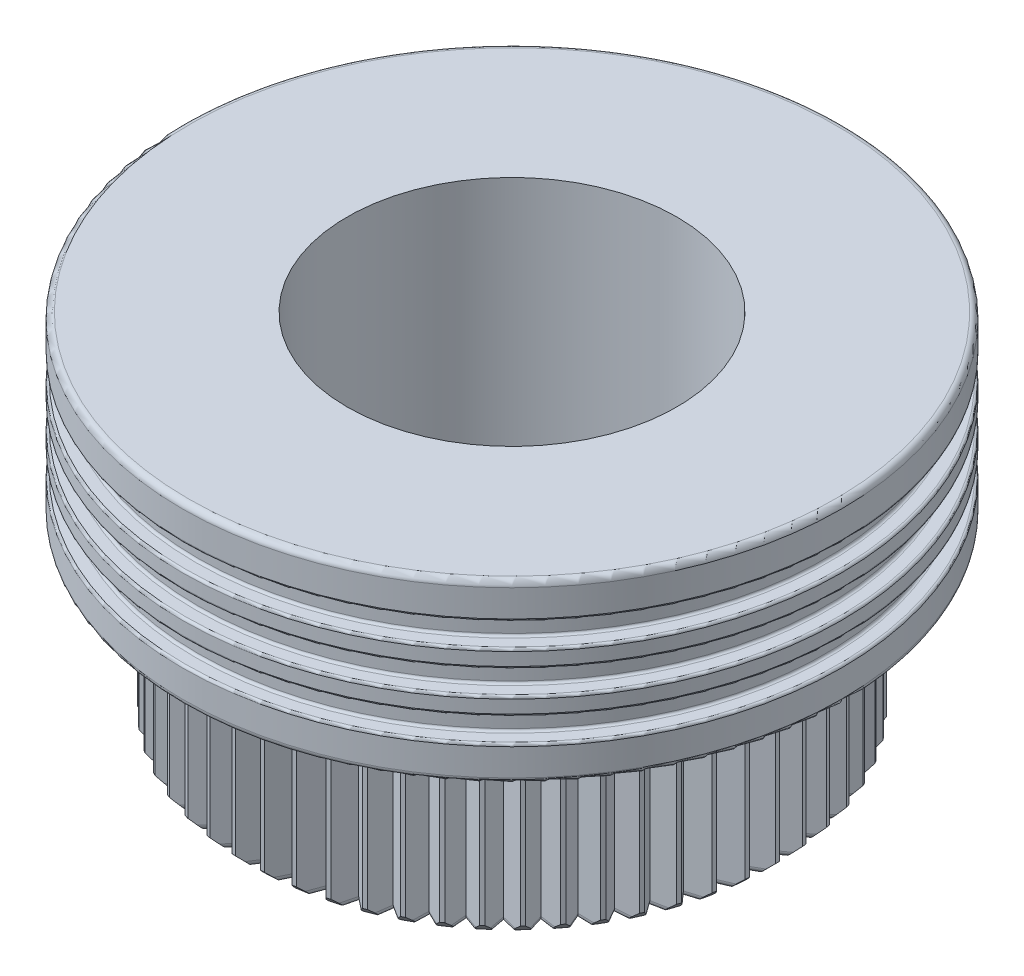
SolidWorks part; units mm, degrees
ref_plane "前视基准面" through (0, 0, 0) normal (0, 0, 1) x (1, 0, 0)
ref_plane "上视基准面" through (0, 0, 0) normal (0, 1, 0) x (1, 0, 0)
ref_plane "右视基准面" through (0, 0, 0) normal (1, 0, 0) x (0, 0, -1)
sketch "草图1" plane through (0, 0, 0) normal (0, 1, 0) x (1, 0, 0)
  circle A0 centre (0, 0) radius 2.25
  circle A1 centre (0, 0) radius 1.2
  dimension "D1" = 2.4
  dimension "D2" = 4.5
extrude "凸台-拉伸1" add sketch "草图1" along normal blind 1.53
sketch "草图2" plane through (0, 1.53, 0) normal (0, 1, 0) x (1, 0, 0)
  circle A0 centre (0, 0) radius 1.2 construction
  circle A1 centre (0, 0) radius 1.2
  circle A2 centre (0, 0) radius 2.8
  dimension "D1" = 5.6
extrude "凸台-拉伸2" add sketch "草图2" along normal blind 1.5
hole_wizard "M3 螺纹孔1" positions "草图3" profile "草图4" tap size "M3" standard "GB" end condition through all
sketch "草图3" plane through (0, 3.03, 0) normal (0, 1, 0) x (1, 0, 0)
  point P0 (0, 0)
sketch "草图4" plane through (0, 3.03, 0) normal (1, 0, 0) x (0, 0, 1)
  line L0 (0, 0) -> (0, 3.03)
  line L1 (0, 3.03) -> (1.4, 3.03)
  line L2 (1.4, 3.03) -> (1.4, 0)
  line L5 (1.4, 0) -> (0, 0)
  line L11 (0, -6.35) -> (0, 107.95) construction
  dimension "通孔螺纹孔钻头直径" = 2.8
  dimension "通孔螺纹孔钻头深度" = 3.03
cosmetic thread "孔螺蚊线1" parameters "D2"=3
chamfer "倒角1" distance 0.1 angle 45 1 edges at (0, 0, 2.25)
sketch "草图5" plane through (0, 0, 0) normal (0, -1, 0) x (1, 0, 0)
  line L0 (-0.1033, 2.2519) -> (0.0051, 2.0833)
  line L1 (0.0051, 2.0833) -> (0.1135, 2.2519)
  line L2 (0.1135, 2.2519) -> (-0.1033, 2.2519)
  line L3 (0.3563, 2.2264) -> (0.1408, 2.2499)
  line L4 (0.1408, 2.2499) -> (0.2303, 2.0706)
  line L5 (0.2303, 2.0706) -> (0.3563, 2.2264)
  line L6 (0.5949, 2.1749) -> (0.3832, 2.2215)
  line L7 (0.3832, 2.2215) -> (0.4528, 2.0335)
  line L8 (0.4528, 2.0335) -> (0.5949, 2.1749)
  line L9 (0.8266, 2.0978) -> (0.6212, 2.167)
  line L10 (0.6212, 2.167) -> (0.67, 1.9726)
  line L11 (0.67, 1.9726) -> (0.8266, 2.0978)
  line L12 (1.0485, 1.9961) -> (0.8518, 2.0871)
  line L13 (0.8518, 2.0871) -> (0.8794, 1.8886)
  line L14 (0.8794, 1.8886) -> (1.0485, 1.9961)
  line L15 (1.2582, 1.8711) -> (1.0725, 1.9828)
  line L16 (1.0725, 1.9828) -> (1.0784, 1.7825)
  line L17 (1.0784, 1.7825) -> (1.2582, 1.8711)
  line L18 (1.4531, 1.7241) -> (1.2806, 1.8552)
  line L19 (1.2806, 1.8552) -> (1.2648, 1.6554)
  line L20 (1.2648, 1.6554) -> (1.4531, 1.7241)
  line L21 (1.631, 1.5568) -> (1.4737, 1.7059)
  line L22 (1.4737, 1.7059) -> (1.4364, 1.509)
  line L23 (1.4364, 1.509) -> (1.631, 1.5568)
  line L24 (1.7898, 1.3714) -> (1.6495, 1.5366)
  line L25 (1.6495, 1.5366) -> (1.5911, 1.3448)
  line L26 (1.5911, 1.3448) -> (1.7898, 1.3714)
  line L27 (1.9276, 1.1698) -> (1.8059, 1.3492)
  line L28 (1.8059, 1.3492) -> (1.7272, 1.1649)
  line L29 (1.7272, 1.1649) -> (1.9276, 1.1698)
  line L30 (2.0427, 0.9546) -> (1.9412, 1.1461)
  line L31 (1.9412, 1.1461) -> (1.843, 0.9713)
  line L32 (1.843, 0.9713) -> (2.0427, 0.9546)
  line L33 (2.134, 0.7281) -> (2.0537, 0.9295)
  line L34 (2.0537, 0.9295) -> (1.9373, 0.7664)
  line L35 (1.9373, 0.7664) -> (2.134, 0.7281)
  line L36 (2.2002, 0.4931) -> (2.1422, 0.702)
  line L37 (2.1422, 0.702) -> (2.0088, 0.5524)
  line L38 (2.0088, 0.5524) -> (2.2002, 0.4931)
  line L39 (2.2406, 0.2523) -> (2.2055, 0.4662)
  line L40 (2.2055, 0.4662) -> (2.0567, 0.332)
  line L41 (2.0567, 0.332) -> (2.2406, 0.2523)
  line L42 (2.2548, 0.0086) -> (2.243, 0.225)
  line L43 (2.243, 0.225) -> (2.0806, 0.1077)
  line L44 (2.0806, 0.1077) -> (2.2548, 0.0086)
  line L45 (2.2425, -0.2352) -> (2.2542, -0.0188)
  line L46 (2.2542, -0.0188) -> (2.08, -0.1179)
  line L47 (2.08, -0.1179) -> (2.2425, -0.2352)
  line L48 (2.2039, -0.4763) -> (2.239, -0.2624)
  line L49 (2.239, -0.2624) -> (2.0551, -0.3421)
  line L50 (2.0551, -0.3421) -> (2.2039, -0.4763)
  line L51 (2.1395, -0.7118) -> (2.1975, -0.5029)
  line L52 (2.1975, -0.5029) -> (2.006, -0.5623)
  line L53 (2.006, -0.5623) -> (2.1395, -0.7118)
  line L54 (2.05, -0.9389) -> (2.1302, -0.7376)
  line L55 (2.1302, -0.7376) -> (1.9335, -0.7759)
  line L56 (1.9335, -0.7759) -> (2.05, -0.9389)
  line L57 (1.9364, -1.1551) -> (2.038, -0.9636)
  line L58 (2.038, -0.9636) -> (1.8383, -0.9804)
  line L59 (1.8383, -0.9804) -> (1.9364, -1.1551)
  line L60 (1.8002, -1.3577) -> (1.9218, -1.1783)
  line L61 (1.9218, -1.1783) -> (1.7215, -1.1734)
  line L62 (1.7215, -1.1734) -> (1.8002, -1.3577)
  line L63 (1.6429, -1.5443) -> (1.7832, -1.3791)
  line L64 (1.7832, -1.3791) -> (1.5845, -1.3526)
  line L65 (1.5845, -1.3526) -> (1.6429, -1.5443)
  line L66 (1.4663, -1.7129) -> (1.6236, -1.5639)
  line L67 (1.6236, -1.5639) -> (1.429, -1.516)
  line L68 (1.429, -1.516) -> (1.4663, -1.7129)
  line L69 (1.2725, -1.8614) -> (1.445, -1.7302)
  line L70 (1.445, -1.7302) -> (1.2567, -1.6616)
  line L71 (1.2567, -1.6616) -> (1.2725, -1.8614)
  line L72 (1.0638, -1.9881) -> (1.2495, -1.8763)
  line L73 (1.2495, -1.8763) -> (1.0697, -1.7877)
  line L74 (1.0697, -1.7877) -> (1.0638, -1.9881)
  line L75 (0.8426, -2.0914) -> (1.0393, -2.0004)
  line L76 (1.0393, -2.0004) -> (0.8701, -1.8929)
  line L77 (0.8701, -1.8929) -> (0.8426, -2.0914)
  line L78 (0.6115, -2.1703) -> (0.8169, -2.1011)
  line L79 (0.8169, -2.1011) -> (0.6604, -1.9759)
  line L80 (0.6604, -1.9759) -> (0.6115, -2.1703)
  line L81 (0.3733, -2.2237) -> (0.585, -2.1771)
  line L82 (0.585, -2.1771) -> (0.4429, -2.0357)
  line L83 (0.4429, -2.0357) -> (0.3733, -2.2237)
  line L84 (0.1307, -2.251) -> (0.3461, -2.2275)
  line L85 (0.3461, -2.2275) -> (0.2202, -2.0717)
  line L86 (0.2202, -2.0717) -> (0.1307, -2.251)
  line L87 (-0.1135, -2.2519) -> (0.1033, -2.2519)
  line L88 (0.1033, -2.2519) -> (-0.0051, -2.0833)
  line L89 (-0.0051, -2.0833) -> (-0.1135, -2.2519)
  line L90 (-0.3563, -2.2264) -> (-0.1408, -2.2499)
  line L91 (-0.1408, -2.2499) -> (-0.2303, -2.0706)
  line L92 (-0.2303, -2.0706) -> (-0.3563, -2.2264)
  line L93 (-0.5949, -2.1749) -> (-0.3832, -2.2215)
  line L94 (-0.3832, -2.2215) -> (-0.4528, -2.0335)
  line L95 (-0.4528, -2.0335) -> (-0.5949, -2.1749)
  line L96 (-0.8266, -2.0978) -> (-0.6212, -2.167)
  line L97 (-0.6212, -2.167) -> (-0.67, -1.9726)
  line L98 (-0.67, -1.9726) -> (-0.8266, -2.0978)
  line L99 (-1.0485, -1.9961) -> (-0.8518, -2.0871)
  line L100 (-0.8518, -2.0871) -> (-0.8794, -1.8886)
  line L101 (-0.8794, -1.8886) -> (-1.0485, -1.9961)
  line L102 (-1.2582, -1.8711) -> (-1.0725, -1.9828)
  line L103 (-1.0725, -1.9828) -> (-1.0784, -1.7825)
  line L104 (-1.0784, -1.7825) -> (-1.2582, -1.8711)
  line L105 (-1.4531, -1.7241) -> (-1.2806, -1.8552)
  line L106 (-1.2806, -1.8552) -> (-1.2648, -1.6554)
  line L107 (-1.2648, -1.6554) -> (-1.4531, -1.7241)
  line L108 (-1.631, -1.5568) -> (-1.4737, -1.7059)
  line L109 (-1.4737, -1.7059) -> (-1.4364, -1.509)
  line L110 (-1.4364, -1.509) -> (-1.631, -1.5568)
  line L111 (-1.7898, -1.3714) -> (-1.6495, -1.5366)
  line L112 (-1.6495, -1.5366) -> (-1.5911, -1.3448)
  line L113 (-1.5911, -1.3448) -> (-1.7898, -1.3714)
  line L114 (-1.9276, -1.1698) -> (-1.8059, -1.3492)
  line L115 (-1.8059, -1.3492) -> (-1.7272, -1.1649)
  line L116 (-1.7272, -1.1649) -> (-1.9276, -1.1698)
  line L117 (-2.0427, -0.9546) -> (-1.9412, -1.1461)
  line L118 (-1.9412, -1.1461) -> (-1.843, -0.9713)
  line L119 (-1.843, -0.9713) -> (-2.0427, -0.9546)
  line L120 (-2.134, -0.7281) -> (-2.0537, -0.9295)
  line L121 (-2.0537, -0.9295) -> (-1.9373, -0.7664)
  line L122 (-1.9373, -0.7664) -> (-2.134, -0.7281)
  line L123 (-2.2002, -0.4931) -> (-2.1422, -0.702)
  line L124 (-2.1422, -0.702) -> (-2.0088, -0.5524)
  line L125 (-2.0088, -0.5524) -> (-2.2002, -0.4931)
  line L126 (-2.2406, -0.2523) -> (-2.2055, -0.4662)
  line L127 (-2.2055, -0.4662) -> (-2.0567, -0.332)
  line L128 (-2.0567, -0.332) -> (-2.2406, -0.2523)
  line L129 (-2.2548, -0.0086) -> (-2.243, -0.225)
  line L130 (-2.243, -0.225) -> (-2.0806, -0.1077)
  line L131 (-2.0806, -0.1077) -> (-2.2548, -0.0086)
  line L132 (-2.2425, 0.2352) -> (-2.2542, 0.0188)
  line L133 (-2.2542, 0.0188) -> (-2.08, 0.1179)
  line L134 (-2.08, 0.1179) -> (-2.2425, 0.2352)
  line L135 (-2.2039, 0.4763) -> (-2.239, 0.2624)
  line L136 (-2.239, 0.2624) -> (-2.0551, 0.3421)
  line L137 (-2.0551, 0.3421) -> (-2.2039, 0.4763)
  line L138 (-2.1395, 0.7118) -> (-2.1975, 0.5029)
  line L139 (-2.1975, 0.5029) -> (-2.006, 0.5623)
  line L140 (-2.006, 0.5623) -> (-2.1395, 0.7118)
  line L141 (-2.05, 0.9389) -> (-2.1302, 0.7376)
  line L142 (-2.1302, 0.7376) -> (-1.9335, 0.7759)
  line L143 (-1.9335, 0.7759) -> (-2.05, 0.9389)
  line L144 (-1.9364, 1.1551) -> (-2.038, 0.9636)
  line L145 (-2.038, 0.9636) -> (-1.8383, 0.9804)
  line L146 (-1.8383, 0.9804) -> (-1.9364, 1.1551)
  line L147 (-1.8002, 1.3577) -> (-1.9218, 1.1783)
  line L148 (-1.9218, 1.1783) -> (-1.7215, 1.1734)
  line L149 (-1.7215, 1.1734) -> (-1.8002, 1.3577)
  line L150 (-1.6429, 1.5443) -> (-1.7832, 1.3791)
  line L151 (-1.7832, 1.3791) -> (-1.5845, 1.3526)
  line L152 (-1.5845, 1.3526) -> (-1.6429, 1.5443)
  line L153 (-1.4663, 1.7129) -> (-1.6236, 1.5639)
  line L154 (-1.6236, 1.5639) -> (-1.429, 1.516)
  line L155 (-1.429, 1.516) -> (-1.4663, 1.7129)
  line L156 (-1.2725, 1.8614) -> (-1.445, 1.7302)
  line L157 (-1.445, 1.7302) -> (-1.2567, 1.6616)
  line L158 (-1.2567, 1.6616) -> (-1.2725, 1.8614)
  line L159 (-1.0638, 1.9881) -> (-1.2495, 1.8763)
  line L160 (-1.2495, 1.8763) -> (-1.0697, 1.7877)
  line L161 (-1.0697, 1.7877) -> (-1.0638, 1.9881)
  line L162 (-0.8426, 2.0914) -> (-1.0393, 2.0004)
  line L163 (-1.0393, 2.0004) -> (-0.8701, 1.8929)
  line L164 (-0.8701, 1.8929) -> (-0.8426, 2.0914)
  line L165 (-0.6115, 2.1703) -> (-0.8169, 2.1011)
  line L166 (-0.8169, 2.1011) -> (-0.6604, 1.9759)
  line L167 (-0.6604, 1.9759) -> (-0.6115, 2.1703)
  line L168 (-0.3733, 2.2237) -> (-0.585, 2.1771)
  line L169 (-0.585, 2.1771) -> (-0.4429, 2.0357)
  line L170 (-0.4429, 2.0357) -> (-0.3733, 2.2237)
  line L171 (-0.1307, 2.251) -> (-0.3461, 2.2275)
  line L172 (-0.3461, 2.2275) -> (-0.2202, 2.0717)
  line L173 (-0.2202, 2.0717) -> (-0.1307, 2.251)
  point P176 (0, 0)
  dimension "D1" = 58
extrude "切除-拉伸1" cut sketch "草图5" against normal up to surface (1.53 mm away) up to face at (0, 1.53, 2.25)
fillet "圆角1" radius 0.05 177 edges at (0, 1.53, 2.8) (0, 3.03, 2.8) (0, 0, 1.4) (2.0437, 0, -0.5506) (2.0322, 0, -0.5916) (2.0358, 0, -0.6913) (1.9722, 0, -0.7683) (1.9563, 0, -0.8078) (1.9492, 0, -0.9073) (1.8776, 0, -0.9771) (1.8575, 0, -1.0146) (1.8396, 0, -1.1128) (1.7609, 0, -1.1743) (1.7369, 0, -1.2095) (1.7085, 0, -1.3051) (1.6236, 0, -1.3578) (1.596, 0, -1.3902) (1.5574, 0, -1.4822) (1.4673, 0, -1.5254) (1.4363, 0, -1.5546) (1.388, 0, -1.6419) (1.2938, 0, -1.6751) (1.2598, 0, -1.7008) (1.2024, 0, -1.7824) (1.1051, 0, -1.8052) (1.0685, 0, -1.827) (1.0026, 0, -1.9019) (0.9034, 0, -1.9141) (0.8647, 0, -1.9319) (0.7911, 0, -1.9992) (0.6912, 0, -2.0005) (0.6508, 0, -2.014) (0.5703, 0, -2.073) (0.4708, 0, -2.0635) (0.4292, 0, -2.0726) (0.3429, 0, -2.1225) (0.245, 0, -2.1023) (0.2026, 0, -2.1068) (0.1114, 0, -2.1471) (0.0162, 0, -2.1165) (-0.0264, 0, -2.1164) (-0.1214, 0, -2.1466) (-0.2127, 0, -2.1058) (-0.255, 0, -2.1011) (-0.3528, 0, -2.1209) (-0.4391, 0, -2.0705) (-0.4807, 0, -2.0613) (-0.58, 0, -2.0703) (-0.6604, 0, -2.0109) (-0.7007, 0, -1.9972) (-0.8005, 0, -1.9954) (-0.874, 0, -1.9277) (-0.9126, 0, -1.9097) (-1.0115, 0, -1.8972) (-1.0773, 0, -1.8219) (-1.1137, 0, -1.7999) (-1.2107, 0, -1.7767) (-1.2679, 0, -1.6948) (-1.3018, 0, -1.6689) (-1.3957, 0, -1.6354) (-1.4437, 0, -1.5477) (-1.4746, 0, -1.5184) (-1.5643, 0, -1.4749) (-1.6026, 0, -1.3826) (-1.6301, 0, -1.35) (-1.7146, 0, -1.2971) (-1.7427, 0, -1.2012) (-1.7665, 0, -1.1659) (-1.8448, 0, -1.1041) (-1.8624, 0, -1.0057) (-1.8822, 0, -0.9681) (-1.9534, 0, -0.8982) (-1.9602, 0, -0.7985) (-1.9758, 0, -0.7589) (-2.0391, 0, -0.6817) (-2.035, 0, -0.5819) (-2.0463, 0, -0.5408) (-2.1008, 0, -0.4573) (-2.086, 0, -0.3584) (-2.0928, 0, -0.3164) (-2.1379, 0, -0.2274) (-2.1125, 0, -0.1308) (-2.1147, 0, -0.0883) (-2.15, 0, 0.005) (-2.1143, 0, 0.0984) (-2.1119, 0, 0.1409) (-2.1368, 0, 0.2375) (-2.0912, 0, 0.3264) (-2.0843, 0, 0.3684) (-2.0986, 0, 0.4671) (-2.0437, 0, 0.5506) (-2.0322, 0, 0.5916) (-2.0358, 0, 0.6913) (-1.9722, 0, 0.7683) (-1.9563, 0, 0.8078) (-1.9492, 0, 0.9073) (-1.8776, 0, 0.9771) (-1.8575, 0, 1.0146) (-1.8396, 0, 1.1128) (-1.7609, 0, 1.1743) (-1.7369, 0, 1.2095) (-1.7085, 0, 1.3051) (-1.6236, 0, 1.3578) (-1.596, 0, 1.3902) (-1.5574, 0, 1.4822) (-1.4673, 0, 1.5254) (-1.4363, 0, 1.5546) (-1.388, 0, 1.6419) (-1.2938, 0, 1.6751) (-1.2598, 0, 1.7008) (-1.2024, 0, 1.7824) (-1.1051, 0, 1.8052) (-1.0685, 0, 1.827) (-1.0026, 0, 1.9019) (-0.9034, 0, 1.9141) (-0.8647, 0, 1.9319) (-0.7911, 0, 1.9992) (-0.6912, 0, 2.0005) (-0.6508, 0, 2.014) (-0.5703, 0, 2.073) (-0.4708, 0, 2.0635) (-0.4292, 0, 2.0726) (-0.3429, 0, 2.1225) (-0.245, 0, 2.1023) (-0.2026, 0, 2.1068) (-0.1114, 0, 2.1471) (-0.0162, 0, 2.1165) (0.0264, 0, 2.1164) (0.1214, 0, 2.1466) (0.2127, 0, 2.1058) (0.255, 0, 2.1011) (0.3528, 0, 2.1209) (0.4391, 0, 2.0705) (0.4807, 0, 2.0613) (0.58, 0, 2.0703) (0.6604, 0, 2.0109) (0.7007, 0, 1.9972) (0.8005, 0, 1.9954) (0.874, 0, 1.9277) (0.9126, 0, 1.9097) (1.0115, 0, 1.8972) (1.0773, 0, 1.8219) (1.1137, 0, 1.7999) (1.2107, 0, 1.7767) (1.2679, 0, 1.6948) (1.3018, 0, 1.6689) (1.3957, 0, 1.6354) (1.4437, 0, 1.5477) (1.4746, 0, 1.5184) (1.5643, 0, 1.4749) (1.6026, 0, 1.3826) (1.6301, 0, 1.35) (1.7146, 0, 1.2971) (1.7427, 0, 1.2012) (1.7665, 0, 1.1659) (1.8448, 0, 1.1041) (1.8624, 0, 1.0057) (1.8822, 0, 0.9681) (1.9534, 0, 0.8982) (1.9602, 0, 0.7985) (1.9758, 0, 0.7589) (2.0391, 0, 0.6817) (2.035, 0, 0.5819) (2.0463, 0, 0.5408) (2.1008, 0, 0.4573) (2.086, 0, 0.3584) (2.0928, 0, 0.3164) (2.1379, 0, 0.2274) (2.1125, 0, 0.1308) (2.1147, 0, 0.0883) (2.15, 0, -0.005) (2.1143, 0, -0.0984) (2.1119, 0, -0.1409) (2.1368, 0, -0.2375) (2.0912, 0, -0.3264) (2.0843, 0, -0.3684) (2.0986, 0, -0.4671)
ref_plane "基准面1" through (0, 1.83, 0) normal (0, 1, 0) x (1, 0, 0)
sketch "草图6" plane through (0, 1.83, 0) normal (0, 1, 0) x (1, 0, 0)
  circle A0 centre (0, 0) radius 2.8 construction
  circle A1 centre (0, 0) radius 2.8
  circle A2 centre (0, 0) radius 2.6674
extrude "切除-拉伸2" cut sketch "草图6" along normal blind 0.2
pattern_linear "阵列(线性)1" count 3 spacing 0.35 along (0, 1, 0) of "切除-拉伸2"
fillet "圆角2" radius 0.02 12 edges at (0, 1.83, 2.6674) (0, 2.03, 2.6674) (0, 2.18, 2.6674) (0, 2.38, 2.6674) (0, 2.53, 2.6674) (0, 2.73, 2.6674) (0, 2.73, 2.8) (0, 2.53, 2.8) (0, 2.38, 2.8) (0, 2.18, 2.8) (0, 2.03, 2.8) (0, 1.83, 2.8)
sketch "草图7" plane through (0, 1.53, 0) normal (0, -1, 0) x (1, 0, 0)
  circle A0 centre (0, 0) radius 2.25
  circle A1 centre (0, 0) radius 1.4 construction
  circle A2 centre (0, 0) radius 1.4
  dimension "D1" = 4.5
extrude "凸台-拉伸3" add sketch "草图7" along normal blind 0.2
fillet "圆角3" radius 0.02 1 edges at (0, 1.53, 2.25)
